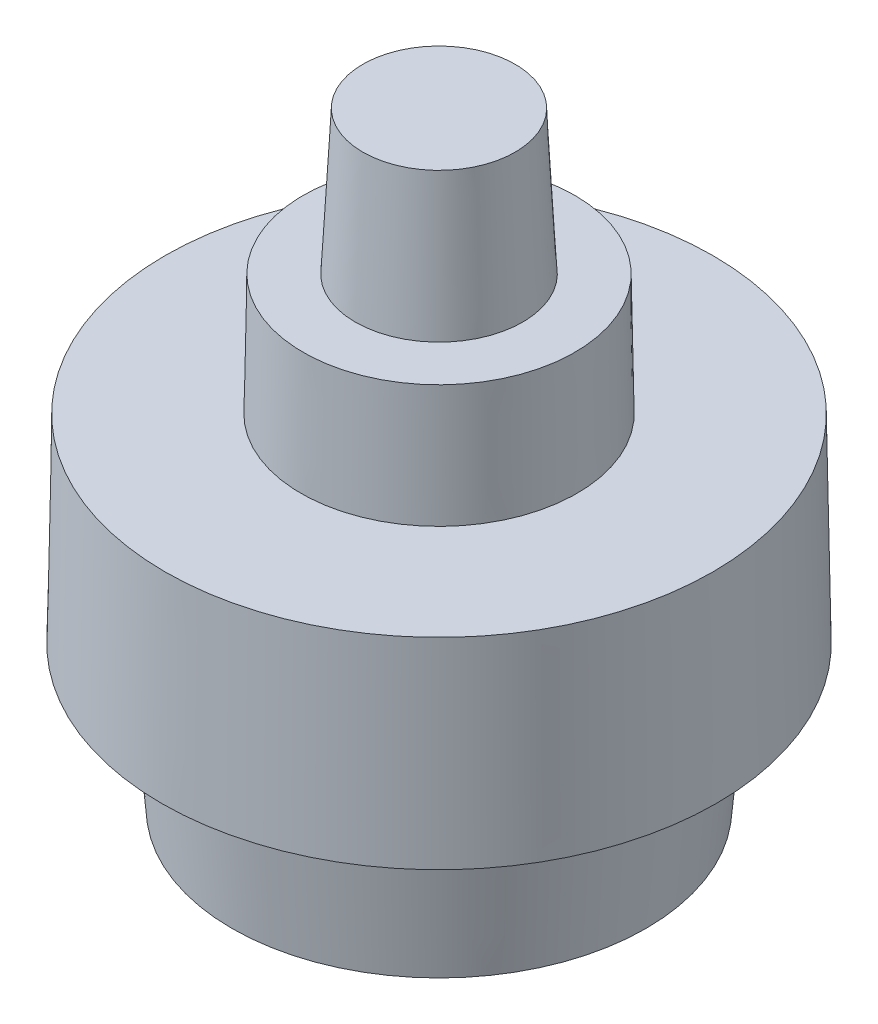
SolidWorks part; units mm, degrees
ref_plane "Front Plane" through (0, 0, 0) normal (0, 0, 1) x (1, 0, 0)
ref_plane "Top Plane" through (0, 0, 0) normal (0, 1, 0) x (1, 0, 0)
ref_plane "Right Plane" through (0, 0, 0) normal (1, 0, 0) x (0, 0, -1)
sketch "Sketch1" plane through (0, 0, 0) normal (0, 0, 1) x (1, 0, 0)
  line L0 (0, 93.4932) -> (0, -90.8962) construction
  line L1 (56, 0) -> (48, 0)
  line L2 (48, 0) -> (48, 28)
  line L3 (48, 28) -> (20, 28)
  line L4 (20, 28) -> (20, 60)
  line L5 (28, 60) -> (20, 60)
  line L6 (56, 38) -> (28, 38)
  line L7 (56, 38) -> (56, 0)
  line L8 (28, 38) -> (28, 60)
  point P9 (54, -5.6767)
  point P10 (54, 34)
  dimension "D2" = 40
  dimension "D1" = 38
  dimension "D3" = 96
  dimension "D4" = 112
  dimension "D5" = 28
  dimension "D6" = 60
  dimension "D7" = 56
revolve "Revolve1" add sketch "Sketch1" angle 360 about L0
scale "Scale1" scale about centroid uniform scaling yes scale factor 1.015
other "Move Face1" face at (0, -0.417, 56.84) face at (0, -0.417, 48.72) face at (0, 28.003, 20.3) face at (0, 60.483, 20.3) offset 3 parameters "D1"=3
sketch "Sketch2" plane through (0, 63.483, 0) normal (0, 1, 0) x (1, 0, 0)
  circle A2 centre (0, 0) radius 17.5
  circle A3 centre (0, 0) radius 17.5
  dimension "D1" = 0.2
extrude "Boss-Extrude1" add sketch "Sketch2" along normal blind 30 draft 3 separate body
sketch "Sketch3" plane through (0, -3.417, 0) normal (0, -1, 0) x (1, 0, 0)
  circle A2 centre (0, 0) radius 45.92
  circle A3 centre (0, 0) radius 45.92
  dimension "D1" = 0.2
extrude "Boss-Extrude2" add sketch "Sketch3" along normal blind 30 draft 5 separate body
shell "Shell1" thickness 0.2 removed face at (0, 63.483, 17.5)
shell "Shell2" thickness 0.2 removed face at (0, -3.417, -45.92)
draft "Draft1" type of draft neutral plane draft angle 1 faces to draft 2 face at (0, 38.153, 56.84) face at (0, 63.483, -28.42) neutral plane through (28.42, 63.483, 0) neutral plane normal (0, 1, 0) parameters "D1"=1
